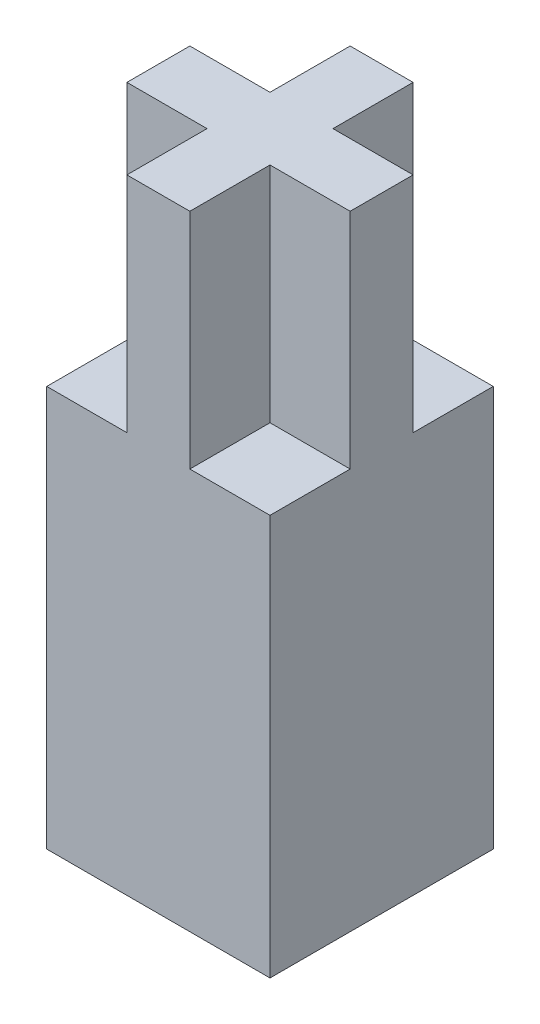
SolidWorks part; units mm, degrees
ref_plane "前视基准面" through (0, 0, 0) normal (0, 0, 1) x (1, 0, 0)
ref_plane "上视基准面" through (0, 0, 0) normal (0, 1, 0) x (1, 0, 0)
ref_plane "右视基准面" through (0, 0, 0) normal (1, 0, 0) x (0, 0, -1)
other "Configuration Table"
sketch "草图5" plane through (0, 0, 0) normal (0, 1, 0) x (-1, 0, 0)
  line L1 (-0.55, -1.95) -> (0.55, -1.95)
  line L2 (-0.55, -1.95) -> (-0.55, 1.95)
  line L3 (-0.55, 1.95) -> (0.55, 1.95)
  line L4 (0.55, -1.95) -> (0.55, 1.95)
  line L5 (-0.55, -1.95) -> (0.55, 1.95) construction
  line L6 (-0.55, 1.95) -> (0.55, -1.95) construction
  line L7 (-1.95, -0.55) -> (1.95, -0.55)
  line L8 (-1.95, -0.55) -> (-1.95, 0.55)
  line L9 (-1.95, 0.55) -> (1.95, 0.55)
  line L10 (1.95, -0.55) -> (1.95, 0.55)
  line L11 (-1.95, -0.55) -> (1.95, 0.55) construction
  line L12 (-1.95, 0.55) -> (1.95, -0.55) construction
  point P0 (0, 0)
  point P6 (0, 0)
  dimension "D1" = 3.9
  dimension "D2" = 1.1
extrude "凸台-拉伸1" add sketch "草图5" along normal blind 3.9 contours L7 L10 L9 L8 | L2 L3 L4 L1
sketch "草图6" plane through (0, 0, 0) normal (0, -1, 0) x (1, 0, 0)
  line L0 (0.55, 1.95) -> (-0.55, 1.95) construction
  line L1 (1.95, -1.95) -> (-1.95, -1.95)
  line L2 (1.95, -1.95) -> (1.95, 1.95)
  line L3 (1.95, 1.95) -> (-1.95, 1.95)
  line L4 (-1.95, -1.95) -> (-1.95, 1.95)
  line L5 (0.55, -1.95) -> (-0.55, -1.95) construction
  line L6 (1.95, -0.55) -> (1.95, 0.55) construction
  line L7 (-1.95, -0.55) -> (-1.95, 0.55) construction
extrude "凸台-拉伸2" add sketch "草图6" along normal blind 7
